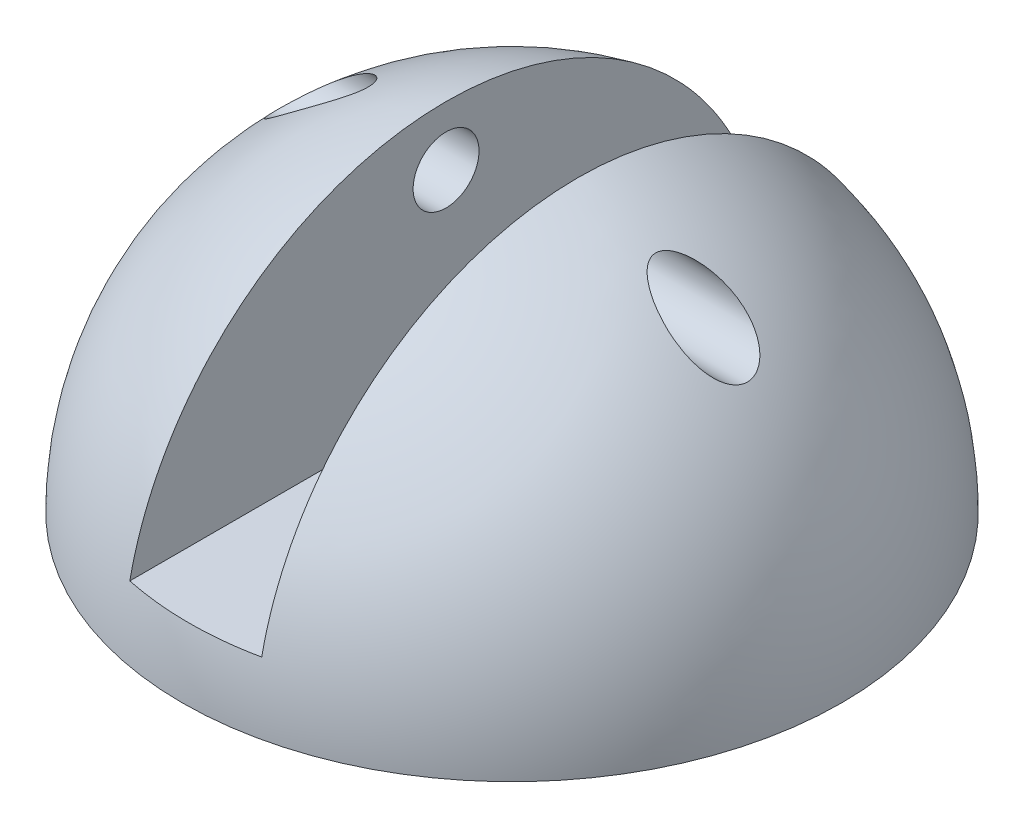
SolidWorks part; units mm, degrees
ref_plane "Front Plane" through (0, 0, 0) normal (0, 0, 1) x (1, 0, 0)
ref_plane "Top Plane" through (0, 0, 0) normal (0, 1, 0) x (1, 0, 0)
ref_plane "Right Plane" through (0, 0, 0) normal (1, 0, 0) x (0, 0, -1)
sketch "Sketch1" plane through (0, 0, 0) normal (0, 1, 0) x (1, 0, 0)
  line L0 (0, -50) -> (0, 50)
  arc A1 (0, 50) -> (0, -50) centre (0, 0) cw
  dimension "D1" = 50
revolve "Revolve1" add sketch "Sketch1" angle 180 about L0 reverse direction yes
sketch "Sketch2" plane through (0, 0, 0) normal (0, 0, 1) x (1, 0, 0)
  line L0 (-50, 0) -> (50, 0) construction
  line L1 (0, 10) -> (10, 10)
  line L2 (0, 10) -> (0, 50)
  line L3 (0, 50) -> (10, 50)
  line L4 (10, 10) -> (10, 50)
  dimension "D1" = 10
  dimension "D2" = 50
  dimension "D3" = 40
extrude "Cut-Extrude1" cut sketch "Sketch2" against normal blind 50 and the other way blind 50
mirror "Mirror1" about plane through (0, 0, 0) normal (1, 0, 0) of "Cut-Extrude1"
sketch "Sketch3" plane through (0, 0, 0) normal (1, 0, 0) x (0, 0, -1)
  line L0 (48.9898, 10) -> (47.9583, 10) construction
  circle A0 centre (0, 40) radius 5
  dimension "D1" = 10
  dimension "D2" = 30
  dimension "D3" = 50
extrude "Cut-Extrude2" cut sketch "Sketch3" against normal blind 50 and the other way blind 50
equation "\"segment width\" = 60"
equation "\"segment support width\"= 20"
equation "\"servo hole\"= 10'arbitrary atm"
equation "\"segment length 1\"= 200"
equation "\"segment length 2\"= 200"
equation "\"segment length 3\"= 200"
equation "\"segment length 4\"= 100"
equation "\"segment length 5\"= 100"
equation "\"base diameter\"= 100"
equation "\"base height\"= 50"
equation "\"D1@Sketch1\"=\"base diameter\" / 2"
equation "\"D1@Sketch2\"=\"segment support width\" / 2"
equation "\"D1@Cut-Extrude1\"=\"base diameter\" / 2"
equation "\"D2@Cut-Extrude1\"=\"base diameter\" / 2"
equation "\"D1@Sketch3\"=\"servo hole\""
equation "\"D2@Sketch3\"=\"segment width\" / 2"
equation "\"D2@Sketch2\"=\"base diameter\" / 2"
equation "\"D3@Sketch2\"=\"base diameter\" - \"segment width\""
equation "\"D3@Sketch3\"=\"base diameter\" / 2"
equation "\"D1@Cut-Extrude2\"=\"base diameter\" / 2"
equation "\"D2@Cut-Extrude2\"=\"base diameter\" / 2"
